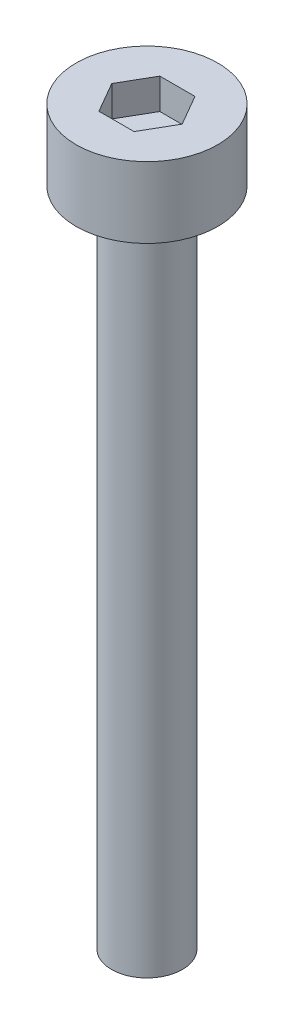
SolidWorks part; units mm, degrees
ref_plane "Front Plane" through (0, 0, 0) normal (0, 0, 1) x (1, 0, 0)
ref_plane "Top Plane" through (0, 0, 0) normal (0, 1, 0) x (1, 0, 0)
ref_plane "Right Plane" through (0, 0, 0) normal (1, 0, 0) x (0, 0, -1)
sketch "Sketch1" plane through (0, 0, 0) normal (0, 1, 0) x (1, 0, 0)
  circle A0 centre (0, 0) radius 1.5
  dimension "D1" = 3
extrude "ScrewShaft" add sketch "Sketch1" along normal blind 28
sketch "Sketch2" plane through (0, 28, 0) normal (0, 1, 0) x (1, 0, 0)
  circle A0 centre (0, 0) radius 3
  dimension "D1" = 6
extrude "Boss-Extrude2" add sketch "Sketch2" along normal blind 3
sketch "Sketch3" plane through (0, 31, 0) normal (0, 1, 0) x (1, 0, 0)
  line L0 (0, 0) -> (0, 1.29) construction
  line L1 (1.4896, 0) -> (0.7448, 1.29)
  line L2 (0.7448, 1.29) -> (-0.7448, 1.29)
  line L3 (-0.7448, 1.29) -> (-1.4896, 0)
  line L4 (-1.4896, 0) -> (-0.7448, -1.29)
  line L5 (-0.7448, -1.29) -> (0.7448, -1.29)
  line L6 (0.7448, -1.29) -> (1.4896, 0)
  circle A0 centre (0, 0) radius 1.29 construction
  dimension "D1" = 2.58
extrude "Cut-Extrude1" cut sketch "Sketch3" against normal blind 1.3
equation "\"X-ROD-SPACING\"=45"
equation "\"Y-ROD-SPACING\"=75"
equation "\"Z-ROD-SPACING\"=17.5"
equation "\"Y-BED-OFFSET\"=2"
equation "\"Y-BED-ROD-INSET\"=3.5"
equation "\"T-SLOT-NUT-FILLET-RADIUS\"=0.5"
equation "\"T-SLOT-SCREW-SHAFT-RADIUS\"=1.55"
equation "\"T-SLOT-SCREW-SHAFT-CUTOUT-LENGTH\"=11"
equation "\"T-SLOT-NUT-DEPTH\"=3.5"
equation "\"T-SLOT-NUT-WIDTH\"=2.85"
equation "\"T-SLOT-NUT-END-DISTANCE\"=8"
equation "\"ACRYLIC-THICKNESS\"=10"
equation "\"ACRYLIC-THICKNESS2\"=4.5"
equation "\"ACRYLIC-TAB-CUTOUT-SIZE\"=\"ACRYLIC-THICKNESS\"+\"ACRYLIC-TAB-TOLERANCE\"*2"
equation "\"ACRYLIC-TAB-WIDTH\"=\"ACRYLIC-THICKNESS\""
equation "\"ACRYLIC-M3-HOLE\"=2.9"
equation "\"SMOOTHROD-CAP-SCREW-DISTANCE\"=20"
equation "\"FRAME-WIDTH-INNER\"=370"
equation "\"NEMA17-HOLE-SPACING\"=31"
equation "\"NEMA17-CENTRAL-CUTOUT\"=22.5"
equation "\"Z-BRACKET-REACH\"=55"
equation "\"TOP-BRACKET-SPACING\"=40"
equation "\"SMOOTHROD-X-LENGTH\"=350"
equation "\"SMOOTHROD-Y-LENGTH\"=350"
equation "\"SMOOTHROD-Z-LENGTH\"=350"
equation "\"SMOOTHROD-TIGHTENING-HEADROOM\"=.25"
equation "\"LEADSCREW-Z-LENGTH\"=300"
equation "\"SCREW-LENGTH-FRAME\"=\"ACRYLIC-THICKNESS\" + 10"
equation "\"SCREW-HEAD-RADIUS\"=6"
equation "\"PRINTED-X-SMOOTHROD-DIAMETER\"=8.8"
equation "\"PRINTED-X-SMOOTHROD-CUTOUT\"=10"
equation "\"PRINTED-X-BASE-HEIGHT\"=10"
equation "\"PRINTED-LM8UU-CUTOUT-SIZE\"=15.5"
equation "\"PRINTED-LM8UU-CUTOUT-LENGTH\"=24.5"
equation "\"PRINTED-X-IDLER-HEIGHT\"=16"
equation "\"PSU-MOUNTING-WIDTH\"=95"
equation "\"PSU-MOUNTING-HEIGHT\"=177"
equation "\"D1@ScrewShaft\"=\"SCREW-LENGTH-EXTRUDER\""
equation "\"D1@Sketch2\"=\"SCREW-HEAD-RADIUS\""
equation "\"Y-BED-SCREW-SPACING\"=209"
equation "\"Y-BED-SCREW-CUTOUT-SLOT-HEIGHT\"=2"
equation "\"Z-ROD-INSET\"=13.5"
equation "\"SCREW-LENGTH-MOTOR\"=\"ACRYLIC-THICKNESS\" + 5"
equation "\"SCREW-LENGTH-EXTRUDER\"=28"
equation "\"Y-BELT-TO-ROD-DISTANCE\"=20"
equation "\"SPOOL-HOLDER-ROD-SPACING\"=150"
equation "\"ACRYLIC-X-CARRIAGE-WIDTH\"=55"
equation "\"ACRYLIC-X-CARRIAGE-HEIGHT\"=75"
equation "\"ACRYLIC-X-CARRIAGE-CENTER-TAB-SPACING\"=14"
